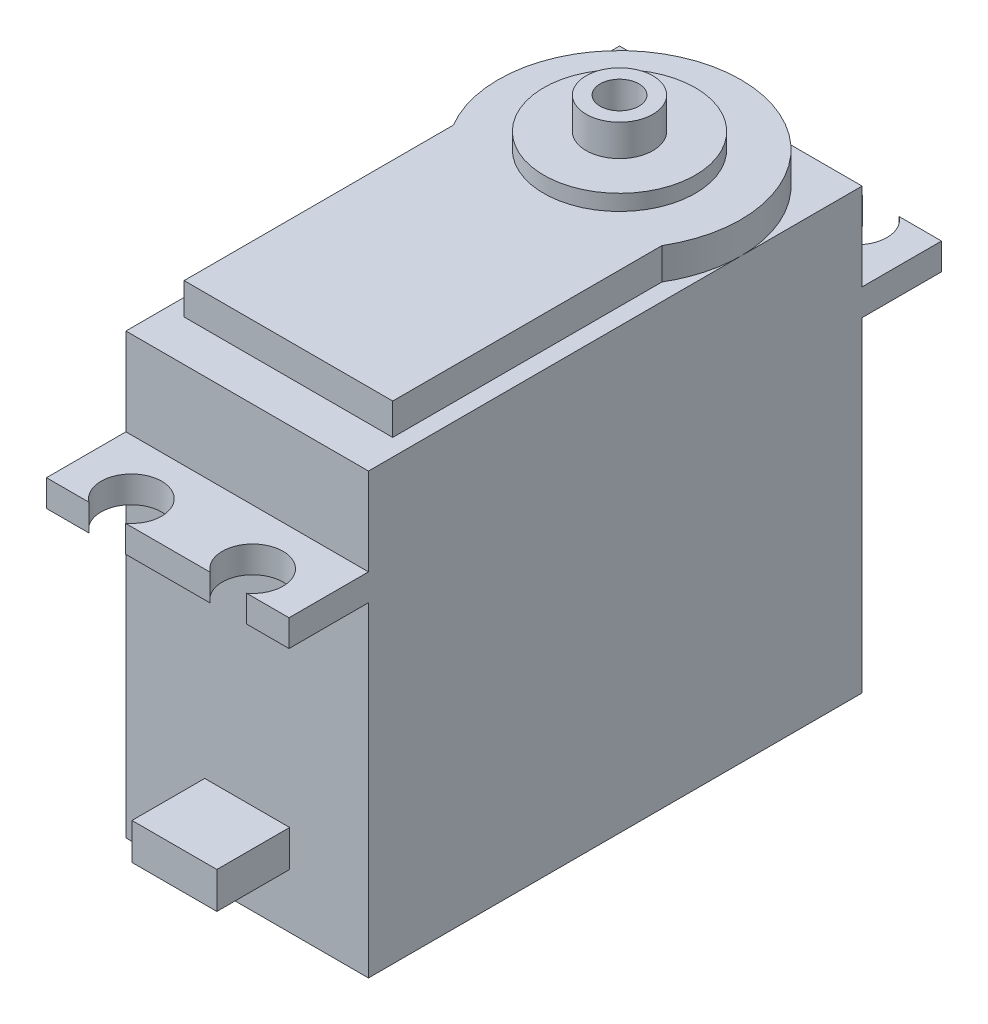
SolidWorks part; units mm, degrees
note: The reader was unsure of these and kept them because the rebuilt part matched: shared geometry of "Sketch3<3>", "Sketch3<4>".
ref_plane "Front Plane" through (0, 0, 0) normal (0, 0, 1) x (1, 0, 0)
ref_plane "Top Plane" through (0, 0, 0) normal (0, 1, 0) x (1, 0, 0)
ref_plane "Right Plane" through (0, 0, 0) normal (1, 0, 0) x (0, 0, -1)
sketch "Sketch1" plane through (0, 0, 0) normal (1, 0, 0) x (0, 0, -1)
  line L1 (-36.346, 39.1934) -> (4.354, 39.1934)
  line L2 (-36.346, 39.1934) -> (-36.346, 2.9934)
  line L3 (-36.346, 2.9934) -> (4.354, 2.9934)
  line L4 (4.354, 39.1934) -> (4.354, 2.9934)
  line L5 (-36.346, 39.1934) -> (4.354, 2.9934) construction
  line L6 (-36.346, 2.9934) -> (4.354, 39.1934) construction
  point P0 (-15.996, 21.0934)
extrude "Boss-Extrude1" add sketch "Sketch1" along normal blind 20
sketch "Sketch2" plane through (0, 0, 0) normal (1, 0, 0) x (0, 0, -1)
  line L0 (4.354, 29.7934) -> (10.904, 29.7934)
  line L1 (-42.896, 29.7934) -> (-36.346, 29.7934)
  line L2 (-42.896, 29.7934) -> (-42.896, 2.9934)
  line L3 (-42.896, 2.9934) -> (-36.346, 2.9934)
  line L4 (-36.346, 29.7934) -> (-36.346, 2.9934)
  line L5 (-42.896, 29.7934) -> (-36.346, 2.9934) construction
  line L6 (-42.896, 2.9934) -> (-36.346, 29.7934) construction
  line L7 (-36.346, 39.1934) -> (-36.346, 2.9934) construction
  line L8 (-36.346, 2.9934) -> (4.354, 2.9934) construction
  line L9 (4.354, 29.7934) -> (4.354, 2.9934)
  line L10 (4.354, 2.9934) -> (10.904, 2.9934)
  line L11 (10.904, 29.7934) -> (10.904, 2.9934)
  line L12 (4.354, 29.7934) -> (10.904, 2.9934) construction
  line L13 (4.354, 2.9934) -> (10.904, 29.7934) construction
  line L14 (4.354, 2.9934) -> (4.354, 39.1934) construction
  line L16 (-42.896, 31.9934) -> (-36.346, 31.9934)
  line L17 (-42.896, 31.9934) -> (-42.896, 29.7934)
  line L18 (-42.896, 29.7934) -> (-36.346, 29.7934)
  line L19 (-36.346, 31.9934) -> (-36.346, 29.7934)
  line L20 (-42.896, 31.9934) -> (-36.346, 29.7934) construction
  line L21 (-42.896, 29.7934) -> (-36.346, 31.9934) construction
  line L22 (4.354, 29.7934) -> (10.904, 29.7934)
  line L23 (4.354, 29.7934) -> (4.354, 31.9934)
  line L24 (4.354, 31.9934) -> (10.904, 31.9934)
  line L25 (10.904, 29.7934) -> (10.904, 31.9934)
  line L26 (4.354, 29.7934) -> (10.904, 31.9934) construction
  line L27 (4.354, 31.9934) -> (10.904, 29.7934) construction
  point P0 (-39.621, 16.3934)
  point P9 (7.629, 30.8934)
  point P10 (-39.6715, 16.48)
  point P12 (7.629, 16.3934)
  point P17 (11.3806, 14.7921)
  point P20 (-39.621, 30.8934)
extrude "Boss-Extrude2" add sketch "Sketch2" along normal blind 20 contours L19 L16 L17 L1 | L0 L25 L24 L23
sketch "Sketch3" plane through (0, 2.9934, 0) normal (0, 1, 0) x (1, 0, 0)
  line L0 (20, 4.354) -> (0, 4.354) construction
  line L1 (20, 4.354) -> (20, -36.346) construction
  line L2 (0, 4.354) -> (0, -36.346) construction
  line L3 (20, -36.346) -> (0, -36.346) construction
  line L4 (0, -32.946) -> (20, -32.946)
  line L5 (0, -32.946) -> (0, -36.346)
  line L6 (0, -36.346) -> (20, -36.346)
  line L7 (20, -32.946) -> (20, -36.346)
  line L8 (0, -32.946) -> (20, -36.346) construction
  line L9 (0, -36.346) -> (20, -32.946) construction
  line L12 (1.4, -10.7489) -> (1.4, -32.946)
  line L13 (1.4, -32.946) -> (18.6, -32.946)
  line L14 (18.6, -10.7489) -> (18.6, -32.946)
  arc A0 (18.6, -10.7489) -> (1.4, -10.7489) centre (10, -5.646) ccw
  circle A1 centre (10, -5.646) radius 6.25
  circle A2 centre (10, -5.646) radius 2.75
  circle A3 centre (10, -5.646) radius 1.6
  point P8 (10, -34.646)
  point P15 (10, -20.8783)
extrude "Boss-Extrude3" add sketch "Sketch3" along normal blind 38.8 contours A0 L14 L4 L12
extrude "Boss-Extrude4" add sketch "Sketch3<3>" along normal blind 40.1 contours A1 A2 | A3
sketch "Sketch3<3>" plane through (0, 2.9934, 0) normal (0, 1, 0) x (1, 0, 0) same geometry as "Sketch3"
extrude "Boss-Extrude5" add sketch "Sketch3<4>" along normal blind 42.7 contours A2 A3
sketch "Sketch3<4>" plane through (0, 2.9934, 0) normal (0, 1, 0) x (1, 0, 0) same geometry as "Sketch3"
sketch "Sketch5" plane through (0, 0, 0) normal (0, 1, 0) x (1, 0, 0)
  line L0 (10, -40.646) -> (20, -40.646) construction
  line L2 (15, -40.646) -> (15, -38.396) construction
  line L4 (15, -38.396) -> (15, -42.896) construction
  circle A1 centre (15, -40.896) radius 2.5
sketch "Sketch8" plane through (0, 31.9934, 0) normal (0, 1, 0) x (1, 0, 0)
  circle A1 centre (5, -40.896) radius 2.5
extrude "Cut-Extrude1" cut sketch "Sketch5" along normal blind 43.9 contours A1
extrude "Cut-Extrude2" cut sketch "Sketch8" against normal blind 43.9 contours A1
sketch "Sketch10" plane through (0, 0, 0) normal (0, 1, 0) x (1, 0, 0)
  circle A0 centre (5, 8.904) radius 2.5
  circle A1 centre (15, 8.904) radius 2.5
extrude "Cut-Extrude3" cut sketch "Sketch10" along normal blind 43.9
sketch "Sketch12" plane through (0, 0, 36.346) normal (0, 0, 1) x (1, 0, 0)
  line L0 (20, 29.7934) -> (20, 2.9934) construction
  line L1 (0, 8.9934) -> (20, 8.9934)
  line L2 (0, 8.9934) -> (0, 2.9934)
  line L3 (0, 2.9934) -> (20, 2.9934)
  line L4 (20, 8.9934) -> (20, 2.9934)
  line L5 (0, 8.9934) -> (20, 2.9934) construction
  line L6 (0, 2.9934) -> (20, 8.9934) construction
  line L7 (20, 2.9934) -> (0, 2.9934) construction
  line L8 (0, 29.7934) -> (0, 2.9934) construction
  line L9 (10, 2.9934) -> (10, 39.1934) construction
  line L10 (1.4, 39.1934) -> (18.6, 39.1934) construction
  line L12 (6.5, 10.4934) -> (13.5, 10.4934)
  line L13 (6.5, 10.4934) -> (6.5, 7.4934)
  line L14 (6.5, 7.4934) -> (13.5, 7.4934)
  line L15 (13.5, 10.4934) -> (13.5, 7.4934)
  line L16 (6.5, 10.4934) -> (13.5, 7.4934) construction
  line L17 (6.5, 7.4934) -> (13.5, 10.4934) construction
  point P0 (10, 5.9934)
  point P11 (10, 8.9934)
extrude "Boss-Extrude6" add sketch "Sketch12" along normal blind 6 contours L15 L12 L13 L1 | L15 L1 L13 L14
